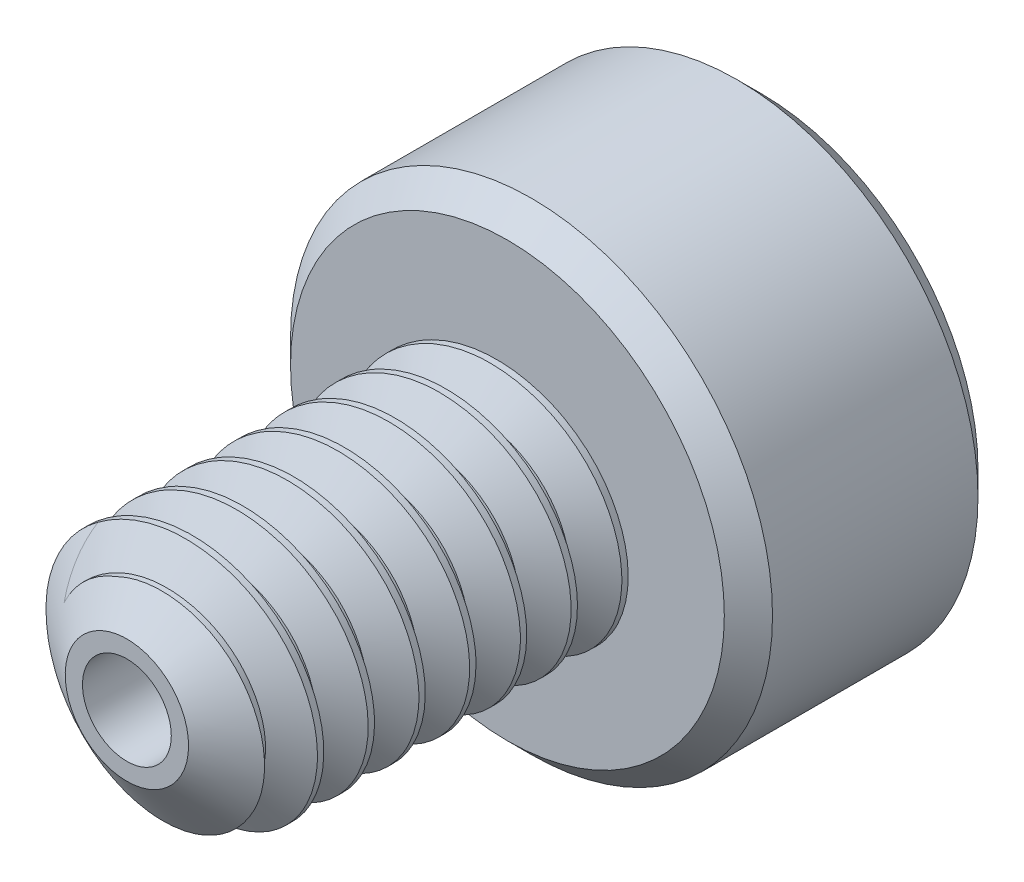
SolidWorks part; units mm, degrees
other "DetailItem1"
ref_plane "Front Plane" through (0, 0, 0) normal (0, 0, 1) x (1, 0, 0)
ref_plane "Top Plane" through (0, 0, 0) normal (0, 1, 0) x (1, 0, 0)
ref_plane "Right Plane" through (0, 0, 0) normal (1, 0, 0) x (0, 0, -1)
sketch "Sketch1" plane through (0, 0, 0) normal (0, 0, 1) x (1, 0, 0)
  circle A0 centre (0, 0) radius 1
  dimension "OD" = 2
extrude "Extrude1" add sketch "Sketch1" against normal blind 3
sketch "Sketch2" plane through (0, 0, 0) normal (0, 0, 1) x (1, 0, 0)
  circle A0 centre (0, 0) radius 1 construction
  circle A1 centre (0, 0) radius 1
curve "Helix/Spiral1" pitch 0.4 height 3.4 radius 1 centre (0, 0, 0) axis (0, 0, -1) start towards (0, 1, 0) parameters "pitch"=0.4
sketch "Sketch3" plane through (0, 0, 0) normal (1, 0, 0) x (0, 0, -1)
  line L0 (-0.35, 1) -> (-0.2, 0.7402)
  line L1 (-0.2, 0.7402) -> (-0.15, 0.7402)
  line L2 (-0.15, 0.7402) -> (0, 1)
  line L3 (-0.35, 1) -> (0, 1)
  line L4 (-0.175, 1) -> (-0.175, 0.7402) construction
  line L5 (-0.275, 0.8701) -> (-0.075, 0.8701) construction
  line L6 (0, 1) -> (0, -1) construction
  dimension "D1" = 0.05
  dimension "D2" = 0.2
  dimension "D3" = 60
sweep "Cut-Sweep1" cut profiles "Sketch3" path "Helix/Spiral1" align with end faces yes
sketch "Sketch4" plane through (0, 0, 0) normal (1, 0, 0) x (0, 0, -1)
  line L0 (0.3598, 1) -> (0, 0.4862)
  line L1 (0, 0.4862) -> (0, 1)
  line L2 (0.3598, 1) -> (0, 1)
  line L3 (-0.35, 1) -> (0, 1) construction
  line L4 (0, 0) -> (7.0209, 0) construction
  dimension "D1" = 55
  dimension "D2" = 0.254
revolve "Cut-Revolve1" cut sketch "Sketch4" angle 360 about L4
sketch "Sketch6" plane through (0, 0, -3) normal (0, 0, -1) x (-1, 0, 0)
  circle A0 centre (0, 0) radius 1.9
  dimension "head dia" = 3.8
extrude "Extrude2" add sketch "Sketch6" along normal blind 2
sketch "Sketch7" plane through (0, 0, -5) normal (0, 0, -1) x (-1, 0, 0)
  line L1 (0, 0.866) -> (-0.75, 0.433)
  line L2 (-0.75, 0.433) -> (-0.75, -0.433)
  line L3 (-0.75, -0.433) -> (0, -0.866)
  line L4 (0, -0.866) -> (0.75, -0.433)
  line L5 (0.75, -0.433) -> (0.75, 0.433)
  line L6 (0.75, 0.433) -> (0, 0.866)
  circle A0 centre (0, 0) radius 0.75 construction
  dimension "hex dia" = 1.5
extrude "Cut-Extrude1" cut sketch "Sketch7" against normal blind 1.125
sketch "Sketch8" plane through (0, 0, -5) normal (0, 0, -1) x (-1, 0, 0)
  circle A0 centre (0, 0) radius 0.866
extrude "Cut-Extrude2" cut sketch "Sketch8" against normal through all draft 45
chamfer "Chamfer1" distance 0.19 angle 45 2 edges at (-1.9, 0, -5) (-1.9, 0, -3)
sketch "Sketch10" plane through (0, 0, -3) normal (0, 0, 1) x (1, 0, 0)
  circle A1 centre (0, 0) radius 1
  circle A2 centre (0, 0) radius 1
  dimension "D1" = 0
ref_plane "Plane1" through (0, 0, 0) normal (0, 0, 1) x (1, 0, 0)
extrude "partial thread" [suppressed] add sketch "Sketch10" along normal up to surface (12.7 mm away) separate body up to plane "Plane1"
chamfer "Chamfer2" [suppressed] distance 0.04 angle 45
combine bodies "Combine1" [suppressed] operation type add bodies to combine 107 108
sketch "Sketch9" plane through (0, 0, 0) normal (1, 0, 0) x (0, 0, -1)
  line L0 (0, 1) -> (0, -1) construction
  line L1 (1, 1) -> (1, -1) construction
  dimension "D1" = 1
sketch "Sketch11" plane through (0, 0, 0) normal (0, 0, 1) x (1, 0, 0)
  circle A0 centre (0, 0) radius 0.35
  dimension "Vent Dia" = 0.7
extrude "Cut-Extrude3" cut sketch "Sketch11" against normal through all
equation "\"D3@Helix/Spiral1\" = \"screw length@Extrude1\"+\"pitch@Helix/Spiral1\""
equation "\"D1@Sketch3\" = \"pitch@Helix/Spiral1\"*.125"
equation "\"D2@Sketch3\" = \"pitch@Helix/Spiral1\"*.5"
equation "\"D1@Cut-Extrude1\" = \"hex dia@Sketch7\"*.75"
equation "\"D1@Chamfer1\" = \"head dia@Sketch6\"*.05"
equation "\"D1@Sketch9\" = \"pitch@Helix/Spiral1\"*2.5"
equation "\"D1@Chamfer2\"=\"OD@Sketch1\"*.02"
